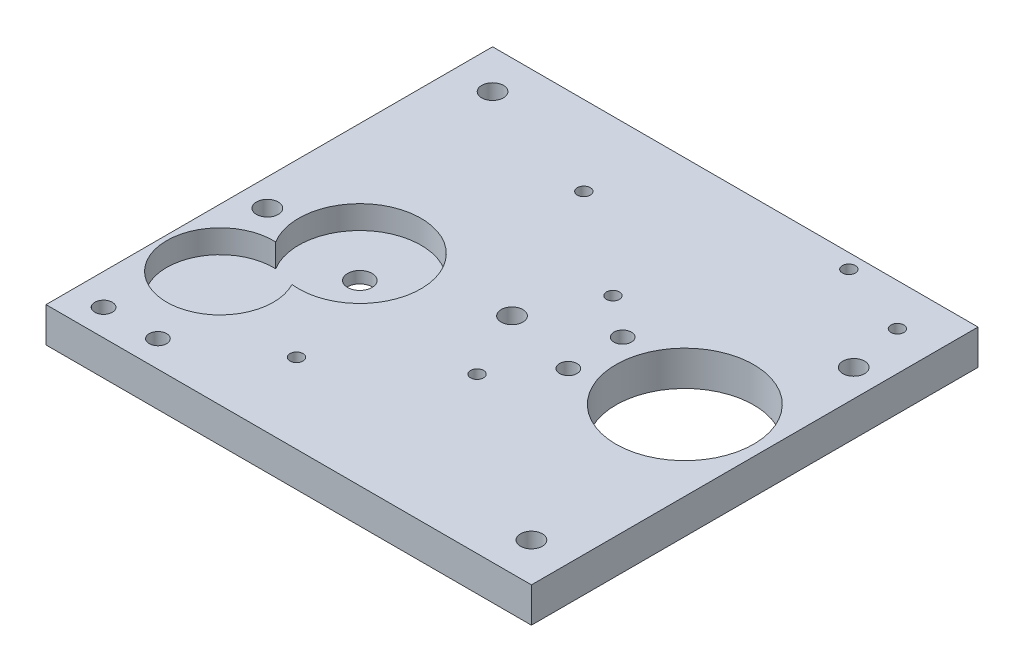
SolidWorks part; units mm, degrees
ref_plane "Front" through (0, 0, 0) normal (0, 0, 1) x (1, 0, 0)
ref_plane "Top" through (0, 0, 0) normal (0, 1, 0) x (1, 0, 0)
ref_plane "Right" through (0, 0, 0) normal (1, 0, 0) x (0, 0, -1)
sketch "Sketch1" plane through (0, 0, 0) normal (0, 1, 0) x (1, 0, 0)
  line L1 (0, 0) -> (125, 0)
  line L2 (0, 0) -> (0, 115)
  line L3 (0, 115) -> (125, 115)
  line L4 (125, 0) -> (125, 115)
  dimension "D1" = 125
  dimension "D2" = 115
extrude "Top_Base" add sketch "Sketch1" along normal blind 9
sketch "Fingers_Position" plane through (0, 9, 0) normal (0, 1, 0) x (1, 0, 0)
  line L0 (74.5, 94.5) -> (39.5, 94.5) construction
  line L1 (74.5, 78.5) -> (19.5, 78.5) construction
  line L2 (74.5, 78.5) -> (74.5, 110.5) construction
  line L3 (74.5, 110.5) -> (19.5, 110.5) construction
  line L4 (19.5, 78.5) -> (19.5, 110.5) construction
  line L5 (74.5, 9.5) -> (19.5, 9.5) construction
  line L6 (74.5, 9.5) -> (74.5, 41.5) construction
  line L7 (74.5, 41.5) -> (19.5, 41.5) construction
  line L8 (19.5, 9.5) -> (19.5, 41.5) construction
  line L10 (39.5, 25.5) -> (74.5, 25.5) construction
  line L11 (125, 115) -> (0, 115) construction
  line L12 (0, 115) -> (0, 0) construction
  dimension "D1" = 55
  dimension "D2" = 32
  dimension "D3" = 69
  dimension "D4" = 4.5
  dimension "D5" = 19.5
  dimension "D6" = 20
sketch "Intermediate_Gear_Position" plane through (0, 9, 0) normal (0, 1, 0) x (1, 0, 0)
  line L0 (0, 51.7935) -> (29.0154, 51.7935) construction
  line L1 (0, 115) -> (0, 0) construction
  line L2 (29.0154, 51.7935) -> (29.0154, 115) construction
  line L3 (125, 115) -> (0, 115) construction
  line L4 (29.0154, 51.7935) -> (29.0154, 0) construction
  line L5 (0, 0) -> (125, 0) construction
  circle A0 centre (29.0154, 51.7935) radius 15.5 construction
  circle A1 centre (29.0154, 51.7935) radius 13.5625
  circle A2 centre (29.0154, 51.7935) radius 13.8125 construction
  dimension "D3" = 31
  dimension "D4" = 27.125
  dimension "D5" = 27.625
  dimension "D1" = 29.0154
  dimension "D2" = 51.7935
sketch "Drive_Gear_Position" plane through (0, 9, 0) normal (0, 1, 0) x (1, 0, 0)
  line L0 (3, 20.8203) -> (27, 20.8203) construction
  line L1 (3, 38.8203) -> (27, 38.8203)
  line L2 (3, 38.8203) -> (3, 2.8203)
  line L3 (3, 2.8203) -> (27, 2.8203)
  line L4 (27, 38.8203) -> (27, 2.8203)
  line L5 (15, 38.8203) -> (15, 2.8203) construction
  line L6 (95.5, 103) -> (95.5, 48) construction
  line L7 (79.5, 103) -> (111.5, 103) construction
  line L8 (79.5, 103) -> (79.5, 48) construction
  line L9 (79.5, 48) -> (111.5, 48) construction
  line L10 (111.5, 103) -> (111.5, 48) construction
  line L11 (77.5, 72) -> (113.5, 72) construction
  line L12 (77.5, 72) -> (77.5, 48) construction
  line L13 (77.5, 48) -> (113.5, 48) construction
  line L14 (113.5, 72) -> (113.5, 48) construction
  line L15 (95.5, 72) -> (95.5, 48) construction
  line L17 (125, 0) -> (125, 115) construction
  line L18 (125, 115) -> (0, 115) construction
  line L20 (0, 115) -> (0, 0) construction
  circle A0 centre (15, 29.8203) radius 9 construction
  circle A1 centre (15, 29.8203) radius 13.5 construction
  circle A2 centre (15, 29.8203) radius 12
  circle A4 centre (15, 29.8203) radius 12.25 construction
  circle A5 centre (29.0154, 51.7935) radius 13.8125 construction
  dimension "D1" = 27
  dimension "D2" = 18
  dimension "D5" = 24
  dimension "D13" = 24.5
  dimension "D3" = 24
  dimension "D4" = 36
  dimension "D6" = 32
  dimension "D7" = 55
  dimension "D8" = 24
  dimension "D9" = 36
  dimension "D10" = 13.5
  dimension "D11" = 12
  dimension "D12" = 3
sketch "Sketch5" plane through (0, 9, 0) normal (0, 1, 0) x (1, 0, 0)
  circle A0 centre (29.0154, 51.7935) radius 15.75
  circle A1 centre (15, 29.8203) radius 13.75
  dimension "D1" = 27.5
  dimension "D2" = 31.5
extrude "Gears_Extrude_Cut" cut sketch "Sketch5" against normal blind 6 contours A0 A1 | A1 A0 | A0 A1 region at (29.3388, 9, -52.3005) region at (21.457, 9, -39.9435) region at (14.6326, 9, -29.2443)
sketch "Sketch7" plane through (0, 9, 0) normal (0, 1, 0) x (1, 0, 0)
  circle A0 centre (29.0154, 51.7935) radius 3.15
  dimension "D1" = 6.3
extrude "Key_Extrude_Cut" cut sketch "Sketch7" against normal through all
sketch "Sketch8" plane through (0, 9, 0) normal (0, 1, 0) x (1, 0, 0)
  line L0 (113.5, 60) -> (77.5, 60) construction
  line L1 (113.5, 72) -> (113.5, 48) construction
  line L2 (77.5, 72) -> (77.5, 48) construction
  circle A0 centre (104.5, 60) radius 9 construction
  circle A1 centre (104.5, 60) radius 17.75
  dimension "D1" = 18
  dimension "D2" = 35.5
extrude "Thumb_Extrude_Cut" cut sketch "Sketch8" against normal through all
sketch "Sketch9" plane through (0, 9, 0) normal (0, 1, 0) x (1, 0, 0)
  line L0 (74.5, 78.5) -> (19.5, 78.5) construction
  line L1 (74.5, 71.5) -> (67.5, 71.5) construction
  line L2 (74.5, 71.5) -> (74.5, 78.5) construction
  line L3 (74.5, 78.5) -> (67.5, 78.5) construction
  line L4 (67.5, 71.5) -> (67.5, 78.5) construction
  line L5 (74.5, 71.5) -> (67.5, 78.5) construction
  line L6 (74.5, 78.5) -> (67.5, 71.5) construction
  line L11 (125, 57.5) -> (0, 57.5) construction
  line L12 (125, 0) -> (125, 115) construction
  line L14 (74.5, 78.5) -> (74.5, 110.5) construction
  line L16 (0, 115) -> (0, 0) construction
  line L17 (74.5, 110.5) -> (19.5, 110.5) construction
  line L18 (74.5, 78.5) -> (47.5, 78.5) construction
  line L19 (74.5, 78.5) -> (74.5, 110.5) construction
  line L20 (74.5, 110.5) -> (47.5, 110.5) construction
  line L21 (47.5, 78.5) -> (47.5, 110.5) construction
  line L26 (74.5, 94.5) -> (39.5, 94.5) construction
  line L27 (40.5, 98) -> (47.5, 98) construction
  line L28 (40.5, 98) -> (40.5, 91) construction
  line L29 (40.5, 91) -> (47.5, 91) construction
  line L30 (47.5, 98) -> (47.5, 91) construction
  line L31 (40.5, 98) -> (47.5, 91) construction
  line L32 (40.5, 91) -> (47.5, 98) construction
  line L33 (27, 2.8203) -> (27, 0.8203) construction
  line L34 (27, 0.8203) -> (22, 0.8203) construction
  line L35 (22, 0.8203) -> (22, 6.8203) construction
  line L36 (77.5, 60) -> (113.5, 60) construction
  line L37 (77.5, 72) -> (77.5, 48) construction
  line L38 (113.5, 72) -> (113.5, 48) construction
  line L39 (77.5, 72) -> (75.5, 72) construction
  line L40 (75.5, 72) -> (75.5, 67) construction
  line L41 (75.5, 67) -> (81.5, 67) construction
  line L42 (111.5, 103) -> (111.5, 107.75) construction
  line L43 (111.5, 107.75) -> (95.5, 107.75) construction
  line L44 (111.5, 107.75) -> (115, 107.75) construction
  line L45 (115, 107.75) -> (115, 104.25) construction
  line L46 (95.5, 107.75) -> (95.5, 111.25) construction
  line L47 (15, 2.8203) -> (15, 38.8203) construction
  circle A0 centre (71, 75) radius 1.675
  circle A2 centre (44, 94.5) radius 1.675
  circle A3 centre (22, 6.8203) radius 2.25
  circle A4 centre (81.5, 67) radius 2.25
  circle A5 centre (95.5, 111.25) radius 1.675
  circle A6 centre (115, 104.25) radius 1.675
  circle A7 centre (71, 40) radius 1.675
  circle A8 centre (44, 20.5) radius 1.675
  circle A9 centre (8, 6.8203) radius 2.25
  circle A10 centre (81.5, 53) radius 2.25
  point P0 (71, 75)
  point P18 (44, 94.5)
  dimension "D3" = 3.35
  dimension "D10" = 4.5
  dimension "D14" = 4.5
  dimension "D1" = 7
  dimension "D2" = 7
  dimension "D4" = 27
  dimension "D5" = 7
  dimension "D6" = 7
  dimension "D7" = 2
  dimension "D8" = 5
  dimension "D9" = 6
  dimension "D11" = 2
  dimension "D12" = 5
  dimension "D13" = 6
  dimension "D15" = 4.75
  dimension "D16" = 16
  dimension "D17" = 3.5
  dimension "D18" = 3.5
  dimension "D19" = 3.5
extrude "Mount_Holes" cut sketch "Sketch9" against normal blind 5
sketch "Sketch11" plane through (0, 9, 0) normal (0, 1, 0) x (1, 0, 0)
  line L0 (0, 115) -> (10, 115) construction
  line L1 (125, 115) -> (0, 115) construction
  line L2 (10, 115) -> (10, 105) construction
  line L3 (125, 0) -> (115, 0) construction
  line L4 (0, 0) -> (125, 0) construction
  line L5 (115, 0) -> (115, 10) construction
  line L6 (0, 57.5) -> (125, 57.5) construction
  line L7 (0, 115) -> (0, 0) construction
  line L8 (125, 0) -> (125, 115) construction
  line L9 (62.5, 115) -> (62.5, 0) construction
  line L10 (125, 115) -> (125, 90) construction
  line L11 (125, 90) -> (118, 90) construction
  line L12 (0, 0) -> (0, 50) construction
  line L13 (0, 50) -> (7, 50) construction
  circle A0 centre (10, 105) radius 2.8
  circle A1 centre (115, 10) radius 2.8
  circle A2 centre (62.5, 57.5) radius 2.8
  circle A3 centre (118, 90) radius 2.8
  circle A4 centre (7, 50) radius 2.8
  dimension "D5" = 5.6
  dimension "D1" = 10
  dimension "D2" = 10
  dimension "D3" = 10
  dimension "D4" = 10
  dimension "D6" = 25
  dimension "D7" = 7
  dimension "D8" = 50
  dimension "D9" = 7
extrude "Connect_Holes" cut sketch "Sketch11" against normal through all
